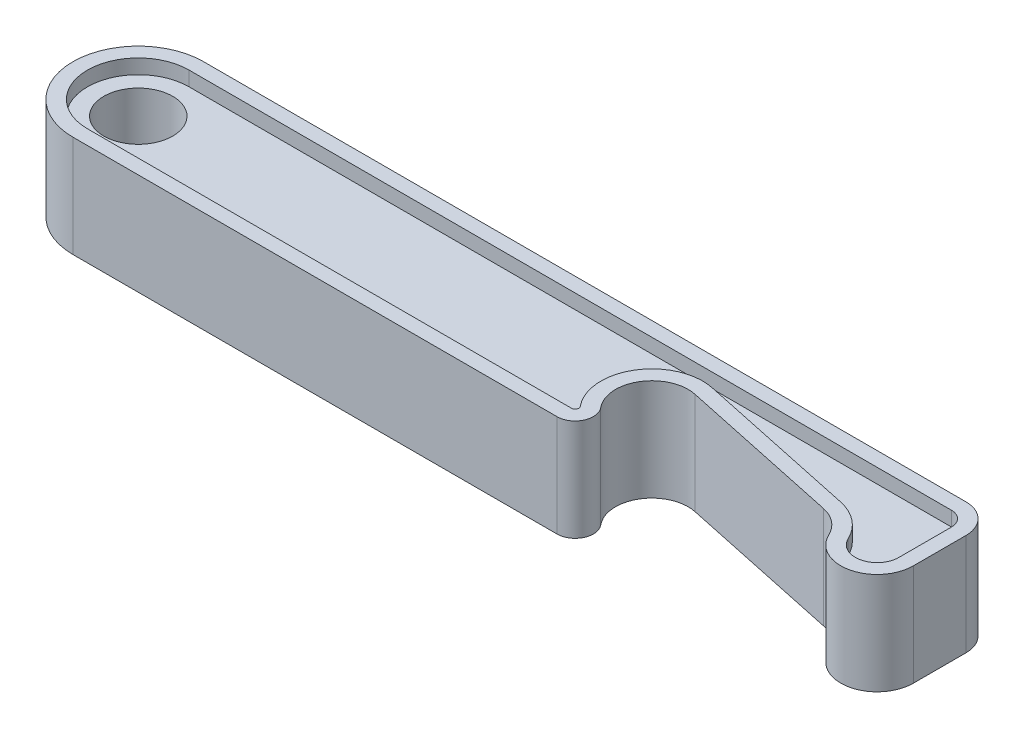
SolidWorks part; units mm, degrees
material "AISI 1020"
ref_plane "Front Plane" through (0, 0, 0) normal (0, 0, 1) x (1, 0, 0)
ref_plane "Top Plane" through (0, 0, 0) normal (0, 1, 0) x (1, 0, 0)
ref_plane "Right Plane" through (0, 0, 0) normal (1, 0, 0) x (0, 0, -1)
sketch "Sketch1" plane through (0, 0, 0) normal (0, 1, 0) x (1, 0, 0)
  line L0 (-50, 9) -> (55, 9)
  line L1 (-59, -9) -> (59, -9) construction
  line L2 (-59, -9) -> (-59, 9) construction
  line L3 (-59, 9) -> (59, 9) construction
  line L4 (59, -9) -> (59, 9) construction
  line L5 (-59, -9) -> (59, 9) construction
  line L6 (-59, 9) -> (59, -9) construction
  line L7 (59, 5) -> (59, -2.2495)
  line L8 (-50, -9) -> (16.671, -9)
  line L9 (23.4879, 3.1733) -> (45.9879, -1.6093)
  line L10 (-50, 7) -> (55, 7)
  line L11 (57, 5) -> (57, -2.2495)
  line L12 (23.9037, 5.1296) -> (46.4037, 0.347)
  line L13 (-50, -7) -> (16.671, -7)
  arc A0 (-50, 9) -> (-50, -9) centre (-50, 0) ccw
  circle A1 centre (-50, 0) radius 4.75
  arc A2 (49.4741, -4.3748) -> (59, -2.2495) centre (54, -2.2495) ccw
  arc A3 (16.671, -9) -> (18.5967, -4.9058) centre (16.671, -6.5) ccw
  arc A4 (18.5967, -4.9058) -> (23.4879, 3.1733) centre (22.4483, -1.7175) cw
  arc A5 (59, 5) -> (55, 9) centre (55, 5) ccw
  arc A6 (49.4741, -4.3748) -> (45.9879, -1.6093) centre (44.9483, -6.5) ccw
  arc A7 (57, 5) -> (55, 7) centre (55, 5) ccw
  arc A8 (51.2845, -3.5247) -> (57, -2.2495) centre (54, -2.2495) ccw
  arc A9 (51.2845, -3.5247) -> (46.4037, 0.347) centre (44.9483, -6.5) ccw
  arc A10 (17.0561, -6.1812) -> (23.9037, 5.1296) centre (22.4483, -1.7175) cw
  arc A11 (16.671, -7) -> (17.0561, -6.1812) centre (16.671, -6.5) ccw
  arc A12 (-50, 7) -> (-50, -7) centre (-50, 0) ccw
  point P0 (0, 0)
  point P24 (49, -2.2495)
  point P25 (0, 0)
  point P26 (24.9875, -9)
  point P27 (29.4966, -0.7512)
  point P28 (35.8377, -6.3869)
  point P29 (24.6799, -6.5)
  point P30 (29.4966, -0.7512)
  point P31 (30.3843, -1.5586)
  point P32 (25.7045, -9)
  point P33 (31.1075, 4.5424)
  point P34 (31.0964, 5)
  point P35 (9.6734, -9)
  point P36 (0, 0)
  point P37 (-21.3586, 12.4478)
  point P38 (12.0706, -6.5)
  point P39 (0, 0)
  point P40 (0, 0)
  dimension "D3" = 9.5
  dimension "D5" = 4
  dimension "D6" = 5
  dimension "D7" = 5
  dimension "D8" = 2.5
  dimension "D4" = 5
  dimension "D1" = 18
  dimension "D2" = 118
  dimension "D9" = 22.5
  dimension "D10" = 12
  dimension "D11" = 2
extrude "Boss-Extrude1" add sketch "Sketch1" along normal mid plane 14 contours A6 A2 L7 A5 L0 A0 L8 A3 A4 L9 A12 L10 A7 L11 A8 A9 L12 A10 A11 L13 region at (2.5, 0, -7.8064)
extrude "Boss-Extrude2" add sketch "Sketch1<4>" along normal mid plane 10 contours L10 A12 L13 A11 A10 L12 A9 A8 L11 A7 A1 region at (-5.9008, 0, -0.6417)
sketch "Sketch1<4>" plane through (0, 0, 0) normal (0, 1, 0) x (1, 0, 0) same geometry as "Sketch1"
equation "\"A\" = 118"
equation "\"B\" = 14"
equation "\"C\"= 2"
equation "\"D2@Sketch1\"=\"A\""
equation "\"D1@Boss-Extrude1\"=\"B\""
equation "\"D1@Boss-Extrude2\"=\"B\"-2*\"C\""
equation "\"D11@Sketch1\"=\"C\""
